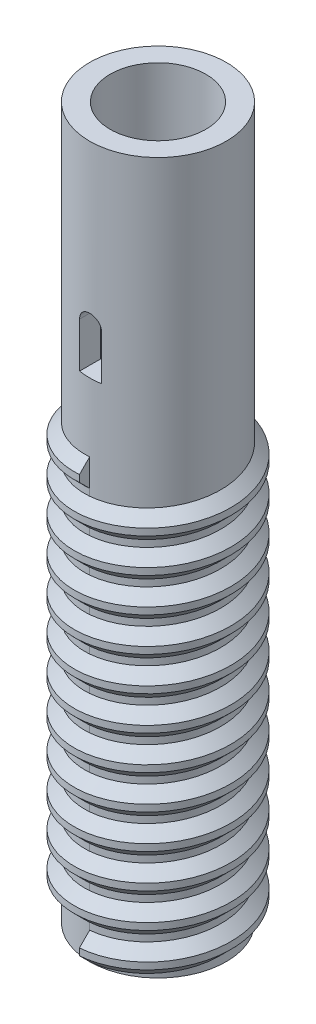
SolidWorks part; units mm, degrees
ref_plane "前视基准面" through (0, 0, 0) normal (0, 0, 1) x (1, 0, 0)
ref_plane "上视基准面" through (0, 0, 0) normal (0, 1, 0) x (1, 0, 0)
ref_plane "右视基准面" through (0, 0, 0) normal (1, 0, 0) x (0, 0, -1)
other "Configuration Table"
sketch "草图1" plane through (0, 0, 0) normal (0, 1, 0) x (1, 0, 0)
  circle A0 centre (0, 0) radius 10
  dimension "D1" = 20
extrude "凸台-拉伸1" add sketch "草图1" along normal blind 14
ref_plane "基准面1" through (0, 2, 0) normal (0, -1, 0) x (-1, 0, 0)
sketch "草图2" plane through (0, 2, 0) normal (0, -1, 0) x (-1, 0, 0)
  circle A0 centre (0, 0) radius 10 construction
  circle A1 centre (0, 0) radius 10
curve "螺旋线/涡状线1" pitch 5 height 60 radius 10 centre (0, 2, 0) axis (0, 1, 0) start towards (0, 0, 1)
sketch "草图3" plane through (0, 0, 0) normal (1, 0, 0) x (0, 0, -1)
  line L0 (-10, 4) -> (-10, 0)
  line L1 (-10, 4) -> (-11.5, 2.5)
  line L2 (-11.5, 2.5) -> (-11.5, 1.5)
  line L3 (-11.5, 1.5) -> (-10, 0)
  point P2 (-10, 2)
  dimension "D1" = 4
  dimension "D2" = 45
  dimension "D3" = 45
  dimension "D4" = 1.5
sweep "扫描1" add profiles "草图3" path "螺旋线/涡状线1"
sketch "草图4" plane through (0, 14, 0) normal (0, 1, 0) x (1, 0, 0)
  circle A0 centre (0, 0) radius 10
  circle A1 centre (0, 0) radius 10 construction
extrude "凸台-拉伸2" add sketch "草图4" along normal blind 90
sketch "草图5" plane through (0, 0, 0) normal (0, -1, 0) x (1, 0, 0)
  circle A0 centre (0, 0) radius 10 construction
  circle A1 centre (0, 0) radius 10 construction
  circle A2 centre (0, 0) radius 7
  dimension "D1" = 3
extrude "切除-拉伸1" cut sketch "草图5" against normal through all
sketch "草图6" plane through (0, 0, 0) normal (0, 0, 1) x (1, 0, 0)
  line L0 (10, 104) -> (-10, 104) construction
  line L1 (10, 104) -> (-10, 104) construction
  line L2 (0, -896) -> (0, 49104) construction
  line L4 (-1.6, 80.6) -> (1.6, 80.6)
  line L5 (-1.6, 80.6) -> (-1.6, 74)
  line L6 (-1.6, 74) -> (1.6, 74)
  line L7 (1.6, 80.6) -> (1.6, 74)
  line L8 (-1.6, 80.6) -> (1.6, 74) construction
  line L9 (-1.6, 74) -> (1.6, 80.6) construction
  circle A0 centre (0, 80.6) radius 1.6
  point P3 (0, 77.3)
  point P5 (0, 104)
  dimension "D1" = 6.6
  dimension "D2" = 3.2
  dimension "D3" = 30
extrude "切除-拉伸2" cut sketch "草图6" against normal through all and the other way through all contours L4 A0 | L4 A0 | A0 L5 L6 L7 region at (0, 81.2791, 0) region at (0, 76.6836, 0) region at (0, 79.9209, 0)
